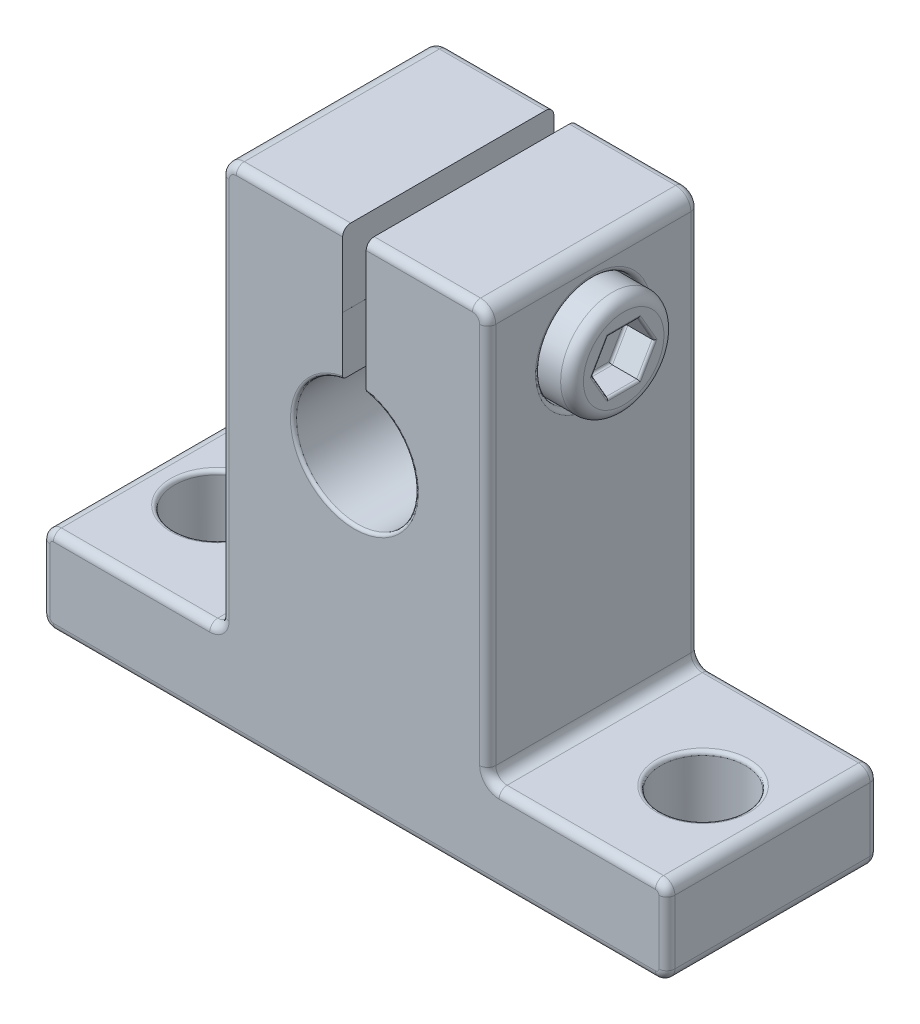
SolidWorks part; units mm, degrees
material "1060 Alloy"
ref_plane "Plano frontal" through (0, 0, 0) normal (0, 0, 1) x (1, 0, 0)
ref_plane "Plano superior" through (0, 0, 0) normal (0, 1, 0) x (1, 0, 0)
ref_plane "Plano direito" through (0, 0, 0) normal (1, 0, 0) x (0, 0, -1)
sketch "Esboço1" plane through (0, 0, 0) normal (0, 0, 1) x (1, 0, 0)
  line L0 (-7.7757, 16.3) -> (-0.7757, 16.3)
  line L1 (-19.815, -16.3) -> (19.815, -16.3)
  line L2 (-20.565, -15.55) -> (-20.565, -11.35)
  line L3 (-19.815, -10.6) -> (-9.5257, -10.6)
  line L4 (20.565, -15.55) -> (20.565, -11.35)
  line L5 (0.7743, 16.3) -> (7.7743, 16.3)
  line L6 (9.5243, -10.6) -> (19.815, -10.6)
  line L7 (8.7743, 15.3) -> (8.7743, -9.85)
  line L8 (-8.7757, 15.3) -> (-8.7757, -9.85)
  line L10 (-0.7757, 11.4644) -> (-0.7757, 16.3)
  line L12 (0.7743, 11.4644) -> (0.7743, 16.3)
  arc A0 (8.7743, 15.3) -> (7.7743, 16.3) centre (7.7743, 15.3) ccw
  arc A1 (-7.7757, 16.3) -> (-8.7757, 15.3) centre (-7.7757, 15.3) ccw
  arc A2 (-20.565, -15.55) -> (-19.815, -16.3) centre (-19.815, -15.55) ccw
  arc A3 (-20.565, -11.35) -> (-19.815, -10.6) centre (-19.815, -11.35) cw
  arc A4 (19.815, -10.6) -> (20.565, -11.35) centre (19.815, -11.35) cw
  arc A5 (19.815, -16.3) -> (20.565, -15.55) centre (19.815, -15.55) ccw
  arc A6 (8.7743, -9.85) -> (9.5243, -10.6) centre (9.5243, -9.85) ccw
  arc A7 (-8.7757, -9.85) -> (-9.5257, -10.6) centre (-9.5257, -9.85) cw
  arc A8 (-0.7757, 11.4644) -> (0.7743, 11.4644) centre (-0.0007, 7.53) ccw
  point P0 (0, 0)
  point P9 (8.7743, 16.3)
  point P15 (-8.7757, 16.3)
  point P18 (-20.565, -16.3)
  point P23 (20.565, -10.6)
  point P26 (20.565, -16.3)
  point P29 (8.7743, -10.6)
  dimension "D1" = 1
  dimension "D4" = 0.75
  dimension "D6" = 8.02
  dimension "D2" = 41.13
  dimension "D3" = 17.55
  dimension "D5" = 5.7
extrude "Ressalto-extrusão1" add sketch "Esboço1" along normal blind 13.9
fillet "Filete2" radius 0.53 34 edges at (-4.2757, 16.3, 13.9) (-8.4828, 16.0071, 13.9) (4.2743, 16.3, 13.9) (8.4814, 16.0071, 13.9) (8.7743, 2.725, 13.9) (8.994, -10.3803, 13.9) (14.6697, -10.6, 13.9) (20.3453, -10.8197, 13.9) (20.565, -13.45, 13.9) (20.3453, -16.0803, 13.9) (0, -16.3, 13.9) (-20.3453, -16.0803, 13.9) (-20.565, -13.45, 13.9) (-20.3453, -10.8197, 13.9) (-14.6703, -10.6, 13.9) (-8.9954, -10.3803, 13.9) (-4.2757, 16.3, 0) (-8.4828, 16.0071, 0) (4.2743, 16.3, 0) (8.4814, 16.0071, 0) (8.7743, 2.725, 0) (8.994, -10.3803, 0) (14.6697, -10.6, 0) (20.3453, -10.8197, 0) (20.565, -13.45, 0) (20.3453, -16.0803, 0) (0, -16.3, 0) (-20.3453, -16.0803, 0) (-20.565, -13.45, 0) (-20.3453, -10.8197, 0) (-14.6703, -10.6, 0) (-8.9954, -10.3803, 0) (-8.7757, 2.725, 13.9) (-8.7757, 2.725, 0)
sketch "Esboço9" plane through (0, 0, 0) normal (0, 0, -1) x (-1, 0, 0)
  circle A1 centre (0.0007, 7.53) radius 4.01
extrude "Ressalto-extrusão4" add sketch "Esboço9" against normal blind 13.9
sketch "Esboço10" plane through (0, 0, 13.9) normal (0, 0, 1) x (1, 0, 0)
  line L0 (-0.7743, 16.3) -> (-0.7743, 7.6445)
  line L1 (0.7743, 11.4644) -> (0.7743, 7.6445)
  line L3 (-0.7743, 16.3) -> (0.7743, 16.3)
  line L4 (0.7743, 11.4644) -> (0.7743, 16.3)
  line L5 (0.7743, 11.4644) -> (0.7743, 16.3)
  line L8 (0.7743, 11.4644) -> (0.7743, 16.3)
  arc A0 (-0.7743, 7.6445) -> (0.7743, 7.6445) centre (0, 3.71) ccw
  dimension "D1" = 8.02
extrude "Corte-extrusão8" cut sketch "Esboço10" against normal blind 20.9 and the other way blind 16 contours L0 A0 L1 | L4 L3 L0 region at (0, 5.4398, 13.9)
fillet "Filete12" radius 0.2 1 edges at (0, -0.3, 0)
fillet "Filete13" radius 0.2 1 edges at (0, -0.3, 13.9)
sketch "Esboço14" plane through (-8.7757, 0, 0) normal (-1, 0, 0) x (0, 0, 1)
  circle A0 centre (6.95, 11.144) radius 1.71
  dimension "D1" = 3.42
extrude "Corte-extrusão9" cut sketch "Esboço14" against normal blind 20.9
fillet "Filete14" radius 0.2 1 edges at (-8.7757, 9.434, 6.95)
sketch "Esboço15" plane through (8.7743, 0, 0) normal (1, 0, 0) x (0, 0, -1)
  circle A0 centre (-6.95, 11.144) radius 3.5
  dimension "D1" = 7
extrude "Corte-extrusão10" cut sketch "Esboço15" against normal blind 3.9
fillet "Filete16" radius 0.3 1 edges at (8.7743, 14.644, 6.95)
sketch "Esboço16" plane through (4.8743, 0, 0) normal (1, 0, 0) x (0, 0, -1)
  circle A0 centre (-6.95, 11.144) radius 3.4
  dimension "D1" = 6.8
extrude "Ressalto-extrusão5" add sketch "Esboço16" along normal blind 5.9
fillet "Filete19" radius 0.75 2 edges at (4.8743, 14.544, 6.95) (10.7743, 14.544, 6.95)
sketch "Esboço17" plane through (10.7743, 0, 0) normal (1, 0, 0) x (0, 0, -1)
  line L1 (-4.9293, 11.144) -> (-5.9396, 12.894)
  line L2 (-5.9396, 12.894) -> (-7.9604, 12.894)
  line L3 (-7.9604, 12.894) -> (-8.9707, 11.144)
  line L4 (-8.9707, 11.144) -> (-7.9604, 9.394)
  line L5 (-7.9604, 9.394) -> (-5.9396, 9.394)
  line L6 (-5.9396, 9.394) -> (-4.9293, 11.144)
  circle A0 centre (-6.95, 11.144) radius 1.75 construction
  point P1 (-6.95, 9.394)
  dimension "D1" = 3.5
extrude "Corte-extrusão11" cut sketch "Esboço17" against normal blind 1.9
fillet "Filete20" radius 0.15 12 edges at (10.7743, 12.019, 5.4345) (10.7743, 12.894, 6.95) (10.7743, 12.019, 8.4655) (10.7743, 10.269, 8.4655) (10.7743, 9.394, 6.95) (10.7743, 10.269, 5.4345) (8.8743, 9.394, 6.95) (8.8743, 10.269, 8.4655) (8.8743, 12.019, 8.4655) (8.8743, 12.894, 6.95) (8.8743, 12.019, 5.4345) (8.8743, 10.269, 5.4345)
sketch "Esboço18" plane through (4.8743, 0, 0) normal (-1, 0, 0) x (0, 0, 1)
  circle A0 centre (6.95, 11.144) radius 1.7
  dimension "D1" = 3.4
extrude "Ressalto-extrusão6" add sketch "Esboço18" along normal blind 12.9
sketch "Esboço19" plane through (0, -16.3, 0) normal (0, -1, 0) x (1, 0, 0)
  circle A0 centre (-16, 6.95) radius 2.79
  circle A1 centre (16, 6.95) radius 2.79
  dimension "D2" = 5.58
  dimension "D3" = 5.58
  dimension "D1" = 32
extrude "Corte-extrusão12" cut sketch "Esboço19" along normal blind 7.9 and the other way blind 17
fillet "Filete21" radius 0.25 1 edges at (18.79, -10.6, 6.95)
fillet "Filete22" radius 0.25 3 edges at (-16, -16.3, 9.74) (16, -16.3, 9.74) (-16, -10.6, 4.16)
